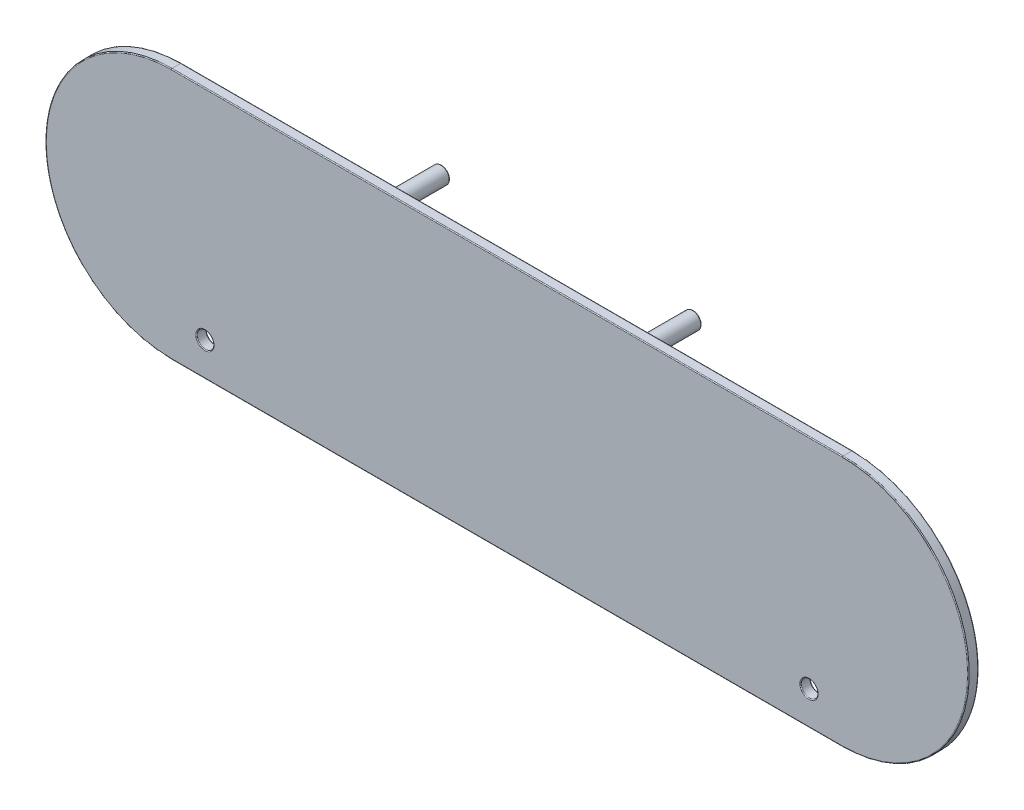
SolidWorks part; units mm, degrees
ref_plane "Front Plane" through (0, 0, 0) normal (0, 0, 1) x (1, 0, 0)
ref_plane "Top Plane" through (0, 0, 0) normal (0, 1, 0) x (1, 0, 0)
ref_plane "Right Plane" through (0, 0, 0) normal (1, 0, 0) x (0, 0, -1)
sketch "Sketch1" plane through (0, 0, 0) normal (0, 0, 1) x (1, 0, 0)
  line L0 (-100, 0) -> (100, 0) construction
  line L1 (-100, 37.5) -> (100, 37.5)
  line L2 (-100, -37.5) -> (100, -37.5)
  line L3 (0, 0) -> (0, -37.5) construction
  arc A0 (-100, 37.5) -> (-100, -37.5) centre (-100, 0) ccw
  arc A1 (100, -37.5) -> (100, 37.5) centre (100, 0) ccw
  circle A3 centre (90, -27.5) radius 2.5
  circle A4 centre (-90, -27.5) radius 2.5
  circle A5 centre (75, -32.5) radius 2.5
  circle A6 centre (37.5, 32.5) radius 2.5
  circle A7 centre (-75, -32.5) radius 2.5
  circle A8 centre (-37.5, 32.5) radius 2.5
  point P2 (0, 0)
  dimension "D3" = 5
  dimension "D6" = 5
  dimension "D9" = 5
  dimension "D1" = 200
  dimension "D2" = 75
  dimension "D4" = 10
  dimension "D5" = 10
  dimension "D7" = 10
  dimension "D8" = 10
  dimension "D10" = 5
  dimension "D11" = 5
  dimension "D12" = 75
  dimension "D13" = 37.5
extrude "Boss-Extrude2" add sketch "Sketch1" along normal blind 3 contours L2 A1 L1 A0 A7 A6 A5 A3 A4 A8 | A8 | A6 | A5 | A7 region at (0, 0.056, 0) region at (75, -32.5, 0) region at (37.5, 32.5, 0) region at (-75, -32.5, 0) region at (-37.5, 32.5, 0)
extrude "Extrude-Thin1" add sketch "Sketch1<4>" against normal blind 15 thin contours A7 | A5 | A6 | A8 thin type one direction reverse wall 2.25
sketch "Sketch1<4>" plane through (0, 0, 0) normal (0, 0, 1) x (1, 0, 0) same geometry as "Sketch1"
fillet "Fillet2" radius 0.25 18 edges at (0, -37.5, 0) (-137.5, 0, 0) (0, 37.5, 0) (-87.5, -27.5, 3) (92.5, -27.5, 3) (-137.5, 0, 3) (0, 37.5, 3) (137.5, 0, 3) (0, -37.5, 3) (77.5, -32.5, -15) (75.25, -32.5, -15) (-75.25, -32.5, -15) (-77.5, -32.5, -15) (-37.75, 32.5, -15) (-40, 32.5, -15) (40, 32.5, -15) (37.75, 32.5, -15) (137.5, 0, 0)
fillet "Fillet3" radius 0.25 6 edges at (-87.5, -27.5, 0) (92.5, -27.5, 0) (40, 32.5, 0) (-35, 32.5, 0) (-72.5, -32.5, 0) (77.5, -32.5, 0)
